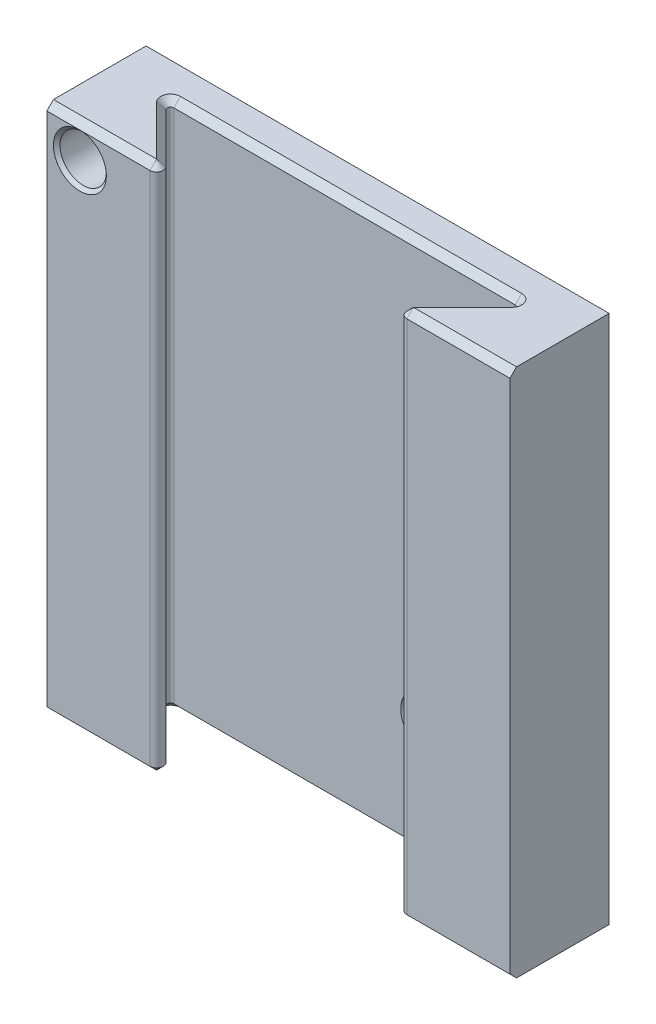
SolidWorks part; units mm, degrees
ref_plane "Top Plane" through (0, 0, 0) normal (0, 0, 1) x (1, 0, 0)
ref_plane "Front Plane" through (0, 0, 0) normal (0, 1, 0) x (1, 0, 0)
ref_plane "Right Plane" through (0, 0, 0) normal (1, 0, 0) x (0, 0, -1)
sketch "Sketch1" plane through (0, 0, 0) normal (0, 0, 1) x (1, 0, 0)
  line L1 (0, 0) -> (70, 0)
  line L2 (0, 0) -> (0, 80)
  line L3 (0, 80) -> (70, 80)
  line L4 (70, 0) -> (70, 80)
  dimension "D1" = 70
  dimension "D2" = 80
extrude "Boss-Extrude1" add sketch "Sketch1" along normal blind 15
sketch "Sketch2" plane through (0, 0, 0) normal (0, -1, 0) x (1, 0, 0)
  line L0 (18, 15) -> (8, 5)
  line L1 (0, 15) -> (70, 15) construction
  line L2 (8, 5) -> (62, 5)
  line L3 (62, 5) -> (52, 15)
  line L4 (52, 15) -> (18, 15)
  line L5 (0, 0) -> (70, 0) construction
  line L6 (70, 15) -> (70, 0) construction
  line L7 (0, 15) -> (0, 0) construction
  point P4 (0, 0)
  dimension "D1" = 45
  dimension "D2" = 45
  dimension "D3" = 5
  dimension "D4" = 8
  dimension "D5" = 8
extrude "Cut-Extrude1" cut sketch "Sketch2" against normal through all
sketch "Sketch3" plane through (0, 0, 15) normal (0, 0, 1) x (1, 0, 0)
  line L0 (0, 80) -> (0, 0) construction
  line L1 (18, 80) -> (0, 80) construction
  circle A0 centre (5, 75) radius 3.5
  point P2 (0, 0)
  dimension "D2" = 7
  dimension "D3" = 5
  dimension "D1" = 5
extrude "Cut-Extrude2" cut sketch "Sketch3" against normal through all
sketch "Sketch4" plane through (0, 0, 5) normal (0, 0, 1) x (1, 0, 0)
  line L0 (8, 80) -> (62, 80) construction
  line L1 (0, 80) -> (0, 0) construction
  circle A0 centre (47.5, 17.5) radius 3.5
  dimension "D1" = 7
  dimension "D3" = 47.5
  dimension "D2" = 62.5
extrude "Cut-Extrude3" cut sketch "Sketch4" against normal through all and the other way through all
fillet "Fillet1" radius 0.5 2 edges at (62, 40, 5) (8, 36.5986, 5)
fillet "Fillet2" radius 1 2 edges at (52, 40, 15) (18, 40, 15)
ref_plane "Plane1" through (45, 0, 0) normal (-1, 0, 0) x (0, 0, 1)
chamfer "Chamfer1" distance 1 angle 45 18 edges at (7.7929, 80, 15) (62.2071, 80, 15) (16.5097, 80, 14.3827) (53.4903, 80, 14.3827) (12.5732, 80, 9.5732) (57.4268, 80, 9.5732) (8.7452, 80, 5.3087) (61.2548, 80, 5.3087) (35, 80, 5) (7.7929, 0, 15) (62.2071, 0, 15) (16.5097, 0, 14.3827) (53.4903, 0, 14.3827) (12.5732, 0, 9.5732) (57.4268, 0, 9.5732) (8.7452, 0, 5.3087) (61.2548, 0, 5.3087) (35, 0, 5)
chamfer "Chamfer2" distance 0.5 angle 45 4 edges at (8.5, 75, 15) (8.5, 75, 0) (51, 17.5, 0) (44, 17.5, 5)
